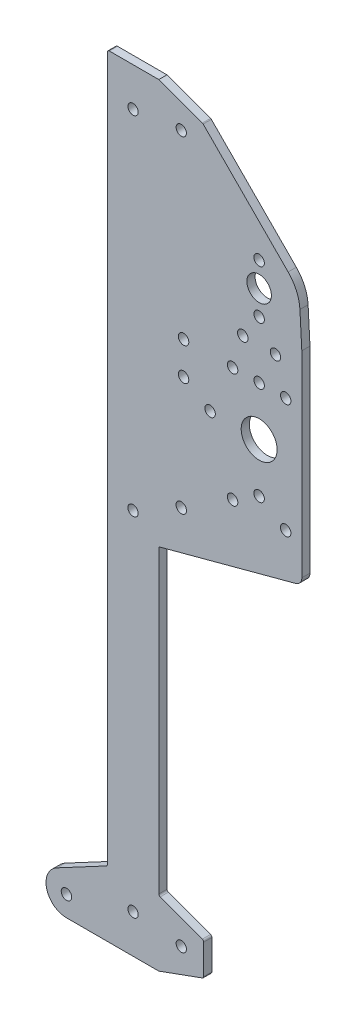
SolidWorks part; units mm, degrees
ref_plane "Front Plane" through (0, 0, 0) normal (0, 0, 1) x (1, 0, 0)
ref_plane "Top Plane" through (0, 0, 0) normal (0, 1, 0) x (1, 0, 0)
ref_plane "Right Plane" through (0, 0, 0) normal (1, 0, 0) x (0, 0, -1)
sketch "Sketch1" plane through (0, 0, 0) normal (0, 0, 1) x (1, 0, 0)
  line L1 (-10, 150) -> (10, 150)
  line L2 (-10, 150) -> (-10, -150)
  line L3 (-10, -150) -> (10, -150)
  line L4 (10, 150) -> (10, -150)
  line L5 (-10, 150) -> (10, -150) construction
  line L6 (-10, -150) -> (10, 150) construction
  point P0 (0, 0)
  dimension "D1" = 300
  dimension "20mm" = 20
extrude "Boss-Extrude1" add sketch "Sketch1" along normal blind 3.175
sketch "Sketch2" plane through (0, 0, 3.175) normal (0, 0, 1) x (1, 0, 0)
  line L0 (10, 150) -> (27.4625, 143.65)
  line L1 (27.4625, 143.65) -> (27.4625, 130.95)
  line L2 (27.4625, 130.95) -> (10, 124.6)
  line L3 (10, -150) -> (10, 150) construction
  line L4 (10, 124.6) -> (10, 150)
  line L5 (10, 150) -> (-10, 150) construction
  line L6 (-10, 0) -> (10, 0) construction
  line L7 (-10, 150) -> (-10, -150) construction
  line L8 (10, -124.6) -> (10, -150)
  line L9 (27.4625, -130.95) -> (10, -124.6)
  line L10 (27.4625, -143.65) -> (27.4625, -130.95)
  line L11 (10, -150) -> (27.4625, -143.65)
  line L12 (18.7312, 140.475) -> (18.7312, 134.125) construction
  circle A1 centre (18.7312, 134.125) radius 5 construction
  circle A2 centre (18.7312, 140.475) radius 2 construction
  circle A4 centre (18.7312, -134.125) radius 5 construction
  circle A5 centre (18.7312, -134.125) radius 2 construction
  circle A6 centre (18.7312, 137.3) radius 2
  circle A7 centre (18.7312, -137.3) radius 2
  point P3 (27.4625, 137.3)
  point P8 (10, 137.3)
  point P13 (18.7312, 127.775)
  point P31 (27.4625, -137.3)
  dimension "D3" = 4
  dimension "D4" = 10
  dimension "D1" = 17.4625
  dimension "2.5" = 25.4
  dimension "D2" = 12.7
  dimension "D5" = 9.525
  dimension "D6" = 9.525
extrude "Boss-Extrude2" add sketch "Sketch2" against normal up to surface (3.175 mm away) up to face at (0, 0, 0)
sketch "Sketch4" plane through (0, 0, 3.175) normal (0, 0, 1) x (1, 0, 0)
  line L0 (0, 150) -> (0, 135) construction
  line L2 (0, 135) -> (0, 0) construction
  line L3 (0, 0) -> (0, -135) construction
  line L4 (0, -135) -> (0, -150) construction
  line L6 (10, 150) -> (-10, 150) construction
  line L7 (-10, -150) -> (10, -150) construction
  circle A0 centre (0, -135) radius 2
  circle A1 centre (0, 0) radius 2
  circle A2 centre (0, 135) radius 2
  dimension "D4" = 4
  dimension "D1" = 15
  dimension "D2" = 135
  dimension "D3" = 135
extrude "Cut-Extrude1" cut sketch "Sketch4" against normal through all
sketch "Sketch5" plane through (0, 0, 3.175) normal (0, 0, 1) x (1, 0, 0)
  line L0 (-10, 111.9) -> (-41.75, 118.25)
  line L1 (-10, 150) -> (-10, -150) construction
  line L2 (-41.75, 118.25) -> (-41.75, 137.3)
  line L3 (-41.75, 137.3) -> (-10, 137.3)
  line L4 (-10, 137.3) -> (-10, 111.9)
  line L5 (10, 150) -> (-10, 150) construction
  line L6 (-41.75, 133.3313) -> (-37.7813, 133.3313) construction
  line L7 (-13.9688, 133.3313) -> (-10, 133.3313) construction
  line L8 (-10, -150) -> (-25.875, -150)
  line L9 (-29.6103, -135.0588) -> (-10, -124.6)
  line L10 (-10, -124.6) -> (-10, -150)
  circle A0 centre (-13.9688, 133.3313) radius 2.032
  circle A1 centre (-13.9688, 122.2188) radius 2.032
  circle A2 centre (-37.7813, 133.3313) radius 2.032
  circle A3 centre (-37.7813, 122.2188) radius 2.032
  arc A4 (-25.875, -150) -> (-29.6103, -135.0588) centre (-25.875, -142.0625) cw
  circle A5 centre (-25.875, -142.0625) radius 2.032
  point P24 (-25.875, 137.3)
  dimension "D5" = 4.064
  dimension "D9" = 4.064
  dimension "D10" = 7.9375
  dimension "D1" = 12.7
  dimension "D2" = 19.05
  dimension "D3" = 25.4
  dimension "D4" = 31.75
  dimension "D6" = 11.1125
  dimension "D7" = 23.8125
  dimension "D8" = 3.9688
  dimension "D11" = 25.4
extrude "Boss-Extrude3" [suppressed] add sketch "Sketch5" against normal up to surface (1.5875 mm away) up to face at (2, -135, 0)
fillet "Fillet3" [suppressed] radius 1.5875
sketch "Sketch6" plane through (0, 0, 3.175) normal (0, 0, 1) x (1, 0, 0)
  line L0 (-10, -124.6) -> (-10, -150) construction
  line L1 (-10, -150) -> (-25.875, -150) construction
  line L2 (-29.6103, -135.0588) -> (-10, -124.6) construction
  line L3 (-10, -124.6) -> (-10, -150)
  line L4 (-10, -150) -> (-25.875, -150)
  line L5 (-29.6103, -135.0588) -> (-10, -124.6)
  circle A0 centre (-25.875, -142.0625) radius 2.032 construction
  arc A1 (-29.6103, -135.0588) -> (-25.875, -150) centre (-25.875, -142.0625) ccw construction
  circle A2 centre (-25.875, -142.0625) radius 2.032
  arc A3 (-29.6103, -135.0588) -> (-25.875, -150) centre (-25.875, -142.0625) ccw
extrude "Boss-Extrude4" add sketch "Sketch6" against normal up to vertex (3.175 mm away) up to point (-10, -150, 0)
fillet "Fillet4" radius 0.7937 8 edges at (10, 124.6, 1.5875) (27.4625, 130.95, 1.5875) (-10, 150, 1.5875) (27.4625, 143.65, 1.5875) (-10, -124.6, 1.5875) (10, -124.6, 1.5875) (27.4625, -130.95, 1.5875) (27.4625, -143.65, 1.5875)
fillet "Fillet5" [suppressed] radius 1.5875
sketch "Sketch7" plane through (0, 0, 0) normal (0, 0, -1) x (-1, 0, 0)
  line L0 (-27.1212, 143.7462) -> (-65.2212, 117.3147)
  line L1 (-65.5625, 116.6625) -> (-65.5625, 10.1095)
  line L2 (-63.2093, 7.0427) -> (-10, -7.2147)
  line L4 (-10, -7.2147) -> (-10, 124.044)
  line L5 (-27.4625, 143.094) -> (-27.4625, 131.506) construction
  line L6 (-26.94, 130.76) -> (-10.5225, 124.79) construction
  line L7 (-27.4625, 143.094) -> (-27.4625, 131.506)
  line L8 (-26.94, 130.76) -> (-10.5225, 124.79)
  line L9 (-10, 150) -> (9.2063, 150) construction
  line L10 (-10, 150) -> (9.2063, 150) construction
  line L11 (-48.989, 45.225) -> (-48.989, 48.4) construction
  line L12 (-38.6703, 23) -> (-59.3078, 23) construction
  line L13 (-38.6703, 23) -> (-38.6703, 67.45) construction
  line L14 (-38.6703, 67.45) -> (-59.3078, 67.45) construction
  line L15 (-59.3078, 23) -> (-59.3078, 67.45) construction
  line L16 (-38.6703, 23) -> (-59.3078, 67.45) construction
  line L17 (-38.6703, 67.45) -> (-59.3078, 23) construction
  line L18 (-48.989, 99.2) -> (-48.989, 48.4) construction
  line L19 (-10, -124.044) -> (-10, 124.044) construction
  arc A0 (-65.2212, 117.3147) -> (-65.5625, 116.6625) centre (-64.7688, 116.6625) ccw
  arc A1 (-65.5625, 10.1095) -> (-63.2093, 7.0427) centre (-62.3875, 10.1095) ccw
  arc A2 (-26.94, 143.84) -> (-27.4625, 143.094) centre (-26.6688, 143.094) ccw construction
  arc A3 (-27.4625, 131.506) -> (-26.94, 130.76) centre (-26.6688, 131.506) ccw construction
  arc A4 (-10, 124.044) -> (-10.5225, 124.79) centre (-10.7937, 124.044) ccw construction
  arc A5 (-27.1212, 143.7462) -> (-27.4625, 143.094) centre (-26.6688, 143.094) ccw
  arc A6 (-27.4625, 131.506) -> (-26.94, 130.76) centre (-26.6688, 131.506) ccw
  arc A7 (-10, 124.044) -> (-10.5225, 124.79) centre (-10.7937, 124.044) ccw
  arc A8 (10, 149.2063) -> (9.2063, 150) centre (9.2063, 149.2063) ccw construction
  circle A9 centre (-48.989, 99.2) radius 4.7625
  circle A10 centre (-48.989, 48.4) radius 6.985
  circle A11 centre (-59.3078, 67.45) radius 2.032
  circle A12 centre (-59.3078, 23) radius 2.032
  circle A13 centre (-38.6703, 23) radius 2.032
  circle A14 centre (-38.6703, 67.45) radius 2.032
  circle A15 centre (-18.7312, 10.3) radius 2.032
  point P32 (-48.989, 45.225)
  point P45 (-18.7312, 137.3)
  dimension "D4" = 9.525
  dimension "D6" = 13.97
  dimension "D11" = 4.064
  dimension "D15" = 3.175
  dimension "D1" = 38.1
  dimension "D2" = 106.553
  dimension "D3" = 16.5735
  dimension "D5" = 50.8
  dimension "D7" = 3.175
  dimension "D8" = 44.45
  dimension "D9" = 50.8
  dimension "D10" = 20.6375
  dimension "D12" = 75
  dimension "D13" = 127
  dimension "D14" = 33.3375
extrude "Boss-Extrude5" add sketch "Sketch7" against normal up to surface (3.175 mm away) up to face at (2, -135, 3.175)
sketch "Sketch8" plane through (0, 0, 3.175) normal (0, 0, 1) x (1, 0, 0)
  line L0 (48.989, 48.4) -> (48.989, 67.45) construction
  line L1 (48.989, 48.4) -> (29.939, 48.4) construction
  line L2 (48.989, 48.4) -> (48.989, 29.35) construction
  line L3 (48.989, 99.2) -> (48.989, 108.725) construction
  line L4 (48.989, 99.2) -> (48.989, 89.675) construction
  line L5 (19.6203, 67.45) -> (19.6203, 54.75) construction
  circle A0 centre (48.989, 67.45) radius 2.032
  circle A1 centre (29.939, 48.4) radius 2.032
  circle A2 centre (48.989, 29.35) radius 2.032
  circle A3 centre (59.3078, 67.45) radius 2.032 construction
  circle A4 centre (48.989, 108.725) radius 2.032
  circle A5 centre (48.989, 89.675) radius 2.032
  circle A6 centre (19.6203, 54.75) radius 2.032
  circle A7 centre (19.6203, 67.45) radius 2.032
  dimension "D2" = 9.525
  dimension "D1" = 19.05
  dimension "D3" = 12.7
  dimension "D4" = 6.35
  dimension "D5" = 10.3187
extrude "Cut-Extrude2" cut sketch "Sketch8" against normal through all
sketch "Sketch9" plane through (0, 0, 0) normal (0, 0, -1) x (-1, 0, 0)
  line L0 (-27.2321, 143.6532) -> (-60.2559, 110.3836)
  line L2 (-65.5625, 86.5) -> (-64.8416, 100.0438)
  line L3 (-65.5625, 86.5) -> (-65.5625, 116.6625)
  line L4 (-27.1212, 143.7462) -> (-65.2212, 117.3147) construction
  line L5 (-27.1212, 143.7462) -> (-65.2212, 117.3147)
  line L6 (-65.5625, 116.6625) -> (-65.5625, 10.1095) construction
  arc A0 (-26.94, 143.84) -> (-27.1212, 143.7462) centre (-26.6688, 143.094) ccw construction
  arc A1 (-27.1212, 143.7462) -> (-27.2321, 143.6532) centre (-26.6688, 143.094) ccw
  arc A2 (-60.2559, 110.3836) -> (-64.8416, 100.0438) centre (-48.989, 99.2) ccw
  arc A4 (-65.2212, 117.3147) -> (-65.5625, 116.6625) centre (-64.7688, 116.6625) ccw construction
  arc A5 (-65.2212, 117.3147) -> (-65.5625, 116.6625) centre (-64.7688, 116.6625) ccw
  circle A6 centre (-59.3078, 67.45) radius 2.032 construction
  point P1 (-65.0964, 71.55)
  point P9 (-65.5625, 71.6676)
  point P20 (0, 0)
  point P22 (-64.7688, 101.8075)
  point P23 (0, 0)
  dimension "D1" = 15.875
  dimension "D2" = 19.05
extrude "Cut-Extrude3" cut sketch "Sketch9" against normal through all
sketch "Sketch10" plane through (0, 0, 0) normal (0, 0, -1) x (-1, 0, 0)
  line L0 (-55.339, 80.15) -> (-42.639, 80.15) construction
  circle A0 centre (-55.339, 80.15) radius 2.032
  circle A1 centre (-42.639, 80.15) radius 2.032
  circle A2 centre (-59.3078, 67.45) radius 2.032 construction
  point P6 (-48.989, 67.45)
  point P7 (0, 0)
  point P9 (-48.989, 80.15)
  dimension "D1" = 12.7
  dimension "D2" = 12.7
extrude "Cut-Extrude4" cut sketch "Sketch10" against normal through all
